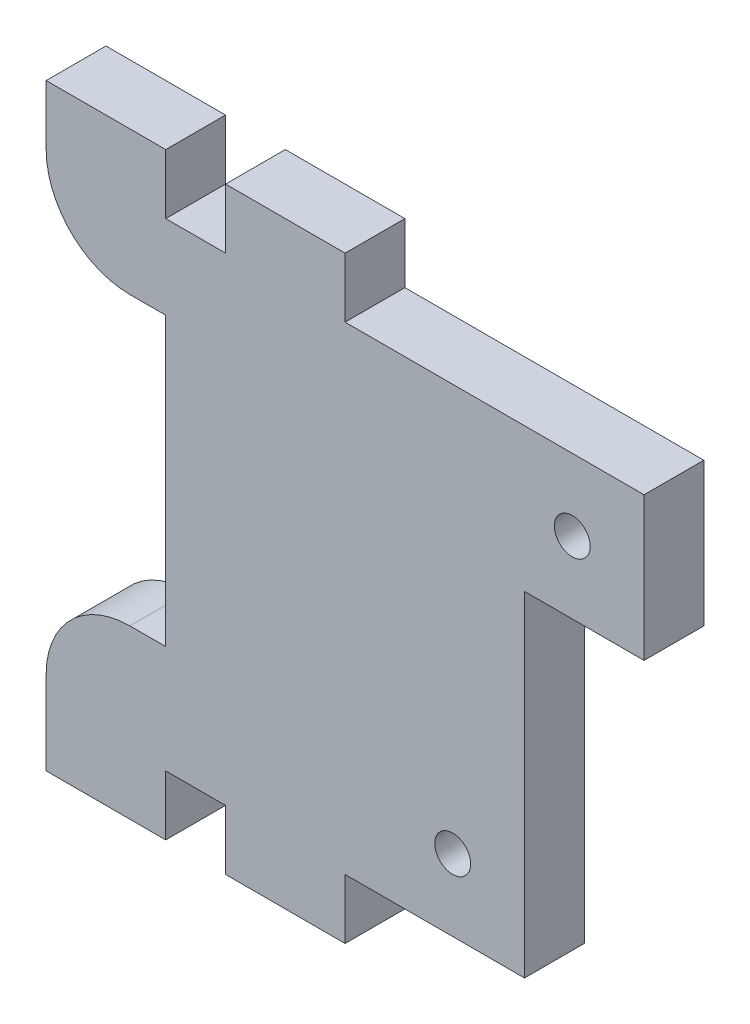
SolidWorks part; units mm, degrees
ref_plane "Plan de face" through (0, 0, 0) normal (0, 0, 1) x (1, 0, 0)
ref_plane "Plan de dessus" through (0, 0, 0) normal (0, 1, 0) x (1, 0, 0)
ref_plane "Plan de droite" through (0, 0, 0) normal (1, 0, 0) x (0, 0, -1)
sketch "Esquisse1" plane through (0, 0, 0) normal (0, 0, 1) x (1, 0, 0)
  line L0 (0, 20) -> (40, 20) construction
  line L1 (10, 0) -> (15, 0)
  line L2 (0, 0) -> (0, 9)
  line L3 (10, 40) -> (15, 40)
  line L4 (50, 28) -> (50, 40)
  line L5 (25, 40) -> (50, 40)
  line L6 (0, 40) -> (0, 45)
  line L7 (0, 45) -> (10, 45)
  line L8 (10, 40) -> (10, 45)
  line L9 (25, 0) -> (40, 0)
  line L10 (15, 40) -> (15, 45)
  line L11 (15, 45) -> (25, 45)
  line L12 (25, 40) -> (25, 45)
  line L13 (25, 0) -> (25, -5)
  line L14 (15, -5) -> (25, -5)
  line L15 (15, 0) -> (15, -5)
  line L16 (10, 0) -> (10, -5)
  line L17 (0, -5) -> (10, -5)
  line L18 (0, 0) -> (0, -5)
  line L19 (0, 33) -> (0, 40)
  line L20 (0, 9) -> (10, 9)
  line L22 (0, 33) -> (10, 33)
  line L23 (10, 9) -> (10, 33)
  line L25 (40, 0) -> (40, 28)
  line L26 (40, 28) -> (50, 28)
  circle A0 centre (44, 34) radius 1.5
  circle A1 centre (34, 6) radius 1.5
  dimension "D9" = 3
  dimension "D11" = 6
  dimension "D1" = 40
  dimension "D2" = 50
  dimension "D3" = 10
  dimension "D4" = 5
  dimension "D5" = 5
  dimension "D6" = 10
  dimension "D7" = 9
  dimension "D8" = 24
  dimension "D10" = 6
  dimension "D12" = 6
  dimension "D13" = 16
  dimension "D14" = 10
  dimension "D15" = 28
extrude "Boss.-Extru.1" add sketch "Esquisse1" along normal blind 5
fillet "Congé1" radius 7 2 edges at (0, 9, 2.5) (0, 33, 2.5)
